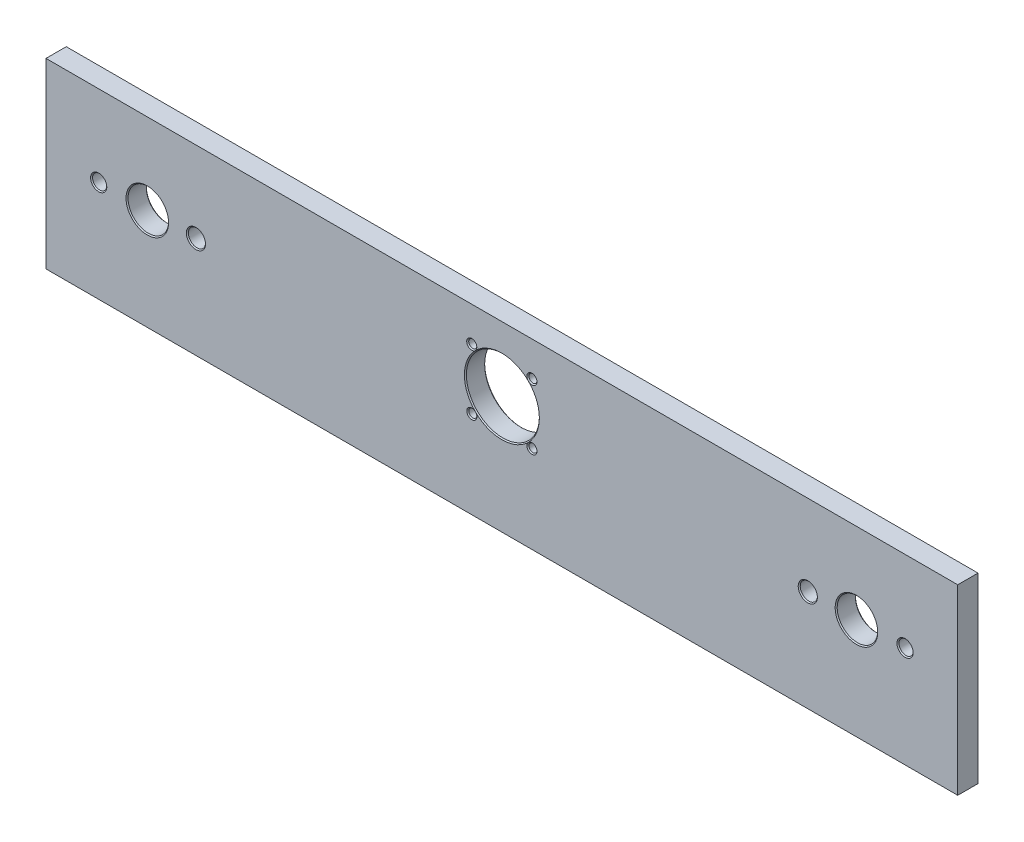
SolidWorks part; units mm, degrees
ref_plane "Alzado" through (0, 0, 0) normal (0, 0, 1) x (1, 0, 0)
ref_plane "Planta" through (0, 0, 0) normal (0, 1, 0) x (1, 0, 0)
ref_plane "Vista lateral" through (0, 0, 0) normal (1, 0, 0) x (0, 0, -1)
sketch "Croquis2" plane through (0, 0, 0) normal (0, 0, 1) x (1, 0, 0)
  line L1 (0, 0) -> (450, 0)
  line L2 (0, 0) -> (0, 90)
  line L3 (0, 90) -> (450, 90)
  line L4 (450, 0) -> (450, 90)
  dimension "D1" = 450
  dimension "D2" = 90
extrude "Saliente-Extruir1" add sketch "Croquis2" along normal blind 10
sketch "Croquis6" plane through (0, 0, 10) normal (0, 0, 1) x (1, 0, 0)
  line L0 (225, 90) -> (225, 0) construction
  line L1 (450, 90) -> (0, 90) construction
  line L2 (0, 0) -> (450, 0) construction
  line L3 (0, 58) -> (450, 58) construction
  line L4 (0, 90) -> (0, 0) construction
  line L5 (450, 0) -> (450, 90) construction
  circle A0 centre (225, 58) radius 18
  circle A1 centre (210.14, 72.8385) radius 2
  circle A2 centre (239.8385, 72.86) radius 2
  circle A3 centre (239.86, 43.1615) radius 2
  circle A4 centre (210.1615, 43.14) radius 2
  point P25 (225, 58)
  dimension "D2" = 36
  dimension "D3" = 4
  dimension "D4" = 4
  dimension "D6" = 21
  dimension "D5" = 21
  dimension "D7" = 21
  dimension "D1" = 32
extrude "Cortar-Extruir1" cut sketch "Croquis6" against normal through all
chamfer "Chaflán5" distance 0.5 angle 45 10 edges at (243, 58, 10) (243, 58, 0) (241.86, 43.1615, 0) (212.1615, 43.14, 0) (241.8385, 72.86, 0) (212.14, 72.8385, 0) (241.86, 43.1615, 10) (241.8385, 72.86, 10) (212.1615, 43.14, 10) (212.14, 72.8385, 10)
sketch "Croquis10" plane through (0, 0, 10) normal (0, 0, 1) x (1, 0, 0)
  line L0 (0, 50) -> (450, 50) construction
  line L1 (0, 90) -> (0, 0) construction
  line L2 (450, 0) -> (450, 90) construction
  line L4 (450, 90) -> (0, 90) construction
  line L5 (225, 90) -> (225, 0) construction
  line L6 (0, 0) -> (450, 0) construction
  circle A0 centre (26, 50) radius 3.5
  circle A1 centre (74, 50) radius 4.2346
  circle A2 centre (376, 50) radius 4.2346
  circle A3 centre (400, 50) radius 10
  circle A4 centre (50, 50) radius 10
  circle A5 centre (424, 50) radius 3.5
  dimension "D1" = 7
  dimension "D2" = 20
  dimension "D3" = 175
  dimension "D4" = 24
  dimension "D6" = 24
  dimension "D5" = 40
extrude "Cortar-Extruir3" cut sketch "Croquis10" against normal through all
chamfer "Chaflán6" distance 0.5 angle 45 12 edges at (29.5, 50, 10) (60, 50, 0) (78.2346, 50, 0) (371.7654, 50, 0) (390, 50, 0) (420.5, 50, 0) (420.5, 50, 10) (390, 50, 10) (371.7654, 50, 10) (78.2346, 50, 10) (60, 50, 10) (29.5, 50, 0)
